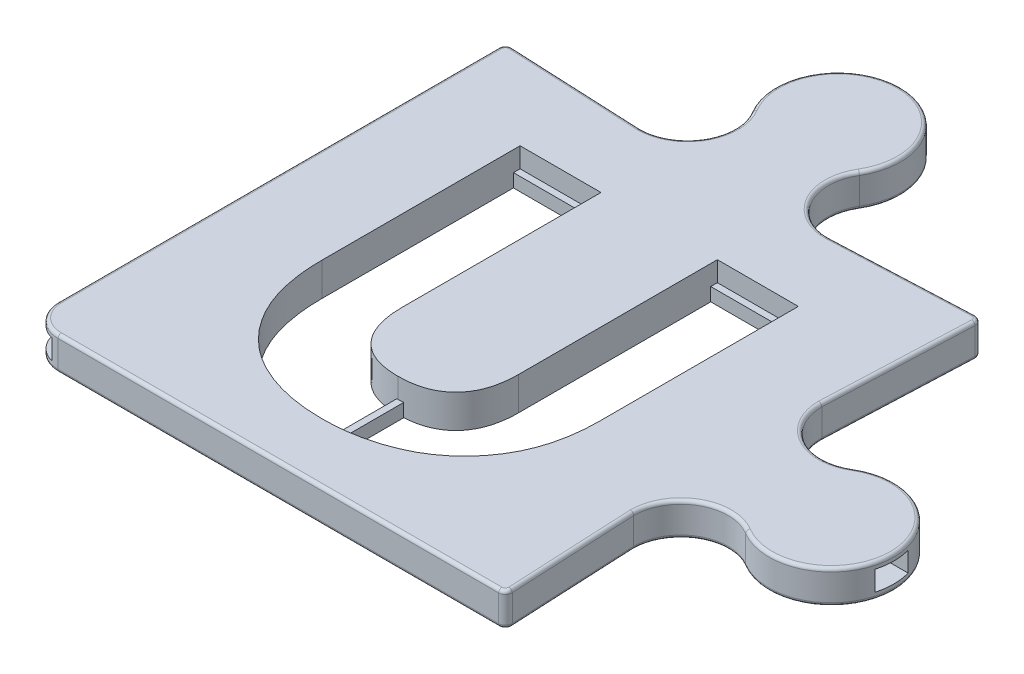
SolidWorks part; units mm, degrees
ref_plane "Front Plane" through (0, 0, 0) normal (0, 0, 1) x (1, 0, 0)
ref_plane "Top Plane" through (0, 0, 0) normal (0, 1, 0) x (1, 0, 0)
ref_plane "Right Plane" through (0, 0, 0) normal (1, 0, 0) x (0, 0, -1)
sketch "Sketch1" plane through (0, 0, 0) normal (0, 1, 0) x (1, 0, 0)
  line L0 (-31, -36) -> (37, -36) construction
  line L1 (-36, 37) -> (-36, -31) construction
  line L2 (-14.1421, 36) -> (-36, 37) construction
  line L3 (37, 37) -> (14.1421, 36) construction
  line L4 (36, 13.1421) -> (37, 37) construction
  line L5 (37, -36) -> (36, -15.1421) construction
  line L6 (-35.4, 36.3719) -> (-35.4, -31)
  line L7 (-36, 36) -> (36, 36) construction
  line L8 (-36, 36) -> (-36, -36) construction
  line L9 (-36, -36) -> (36, -36) construction
  line L10 (36, 36) -> (36, -36) construction
  line L11 (-31, -35.4) -> (36.3705, -35.4)
  line L12 (36.3705, -35.4) -> (35.4, -15.1568)
  line L13 (35.4, 13.155) -> (36.3732, 36.372)
  line L14 (36.3732, 36.372) -> (14.1555, 35.4)
  line L15 (-14.1562, 35.4) -> (-35.4, 36.3719)
  line L16 (-30, -24) -> (30, -24) construction
  line L17 (-30, 29) -> (30, 29) construction
  line L18 (-30, 29) -> (-30, -31) construction
  line L19 (-30, -31) -> (30, -31) construction
  line L20 (30, 29) -> (30, -31) construction
  line L21 (-30, 24) -> (30, 24) construction
  line L22 (-30, 24) -> (-30, -26) construction
  line L23 (-30, -26) -> (30, -26) construction
  line L24 (30, 24) -> (30, -26) construction
  arc A0 (-36, -31) -> (-31, -36) centre (-31, -31) ccw construction
  arc A1 (-14.1421, 36) -> (-8.571, 45.8485) centre (-14.1421, 42.5) ccw construction
  arc A2 (8.571, 45.8485) -> (-8.571, 45.8485) centre (0, 51) ccw construction
  arc A3 (8.571, 45.8485) -> (14.1421, 36) centre (14.1421, 42.5) ccw construction
  arc A4 (36, 13.1421) -> (45.8485, 7.571) centre (42.5, 13.1421) ccw construction
  arc A5 (45.8485, -9.571) -> (45.8485, 7.571) centre (51, -1) ccw construction
  arc A6 (45.8485, -9.571) -> (36, -15.1421) centre (42.5, -15.1421) ccw construction
  arc A7 (-35.4, -31) -> (-31, -35.4) centre (-31, -31) ccw
  arc A8 (46.1576, -9.0567) -> (35.4, -15.1568) centre (42.5, -15.1421) ccw
  arc A9 (46.1576, -9.0567) -> (46.1576, 7.0567) centre (51, -1) ccw
  arc A10 (35.4, 13.155) -> (46.1576, 7.0567) centre (42.5, 13.1421) ccw
  arc A11 (8.0567, 46.1576) -> (14.1555, 35.4) centre (14.1421, 42.5) ccw
  arc A12 (8.0567, 46.1576) -> (-8.0567, 46.1576) centre (0, 51) ccw
  arc A13 (-14.1562, 35.4) -> (-8.0567, 46.1576) centre (-14.1421, 42.5) ccw
  point P32 (36, 0)
  point P34 (0, 36)
  dimension "D5" = 6.5
  dimension "D6" = 10
  dimension "D7" = 6.5
  dimension "D13" = 5
  dimension "D9" = 10
  dimension "D11" = 6.5
  dimension "D12" = 6.5
  dimension "D1" = 72
  dimension "D2" = 1
  dimension "D3" = 1
  dimension "D4" = 15
  dimension "D8" = 1
  dimension "D10" = 35
  dimension "D14" = 15
  dimension "D15" = 36
  dimension "D16" = 1
  dimension "D18" = 60
  dimension "D19" = 60
  dimension "D20" = 5
  dimension "D21" = 6
  dimension "D22" = 5
  dimension "D23" = 50
  dimension "D24" = 2
  dimension "D17" = 0.6
extrude "Boss-Extrude1" add sketch "Sketch1" along normal blind 5
sketch "Sketch6" plane through (0, 0, 0) normal (0, -1, 0) x (1, 0, 0)
  line L0 (-35.4, -36.3719) -> (-35.4, 31) construction
  line L1 (-35.4, 17.9) -> (-27.4, 17.9)
  line L2 (-35.4, 17.9) -> (-35.4, -16.1)
  line L3 (-35.4, -16.1) -> (-27.4, -16.1)
  line L4 (-27.4, 17.9) -> (-27.4, -16.1)
  line L5 (-31, 35.4) -> (36.3705, 35.4) construction
  line L6 (-35.4, 14.65) -> (-30.4, 14.65)
  line L7 (-35.4, 14.65) -> (-35.4, -12.85)
  line L8 (-35.4, -12.85) -> (-30.4, -12.85)
  line L9 (-30.4, 14.65) -> (-30.4, -12.85)
  point P15 (-27.4, 0.9)
  point P16 (-30.4, 0.9)
  line M28 (-35.4, 31) -> (-35.4, -36.3719)
  dimension "D1" = 8
  dimension "D2" = 20.75
  dimension "D3" = 27.5
  dimension "D4" = 5
  dimension "D5" = 34
extrude "Cut-Extrude3" cut sketch "Sketch6" against normal blind 3 from offset 1 contours L6 L9 L8 L3 L4 L1 M28 | L9 L6 L2 L8 region at (-29.8665, 0, 0.9) region at (-32.9, 0, 0.9) offset against normal yes
extrude "Cut-Extrude4" cut sketch "Sketch6<3>" against normal up to next contours L9 L6 L2 L8 region at (-32.9, 0, 0.9)
sketch "Sketch6<3>" plane through (0, 0, 0) normal (0, -1, 0) x (1, 0, 0) same geometry as "Sketch6"
sketch "Sketch8" plane through (0, 0, 0) normal (0, -1, 0) x (1, 0, 0)
  line L1 (-2.5, -51.4) -> (2.5, -51.4)
  line L2 (-2.5, -51.4) -> (-2.5, -60.4)
  line L3 (-2.5, -60.4) -> (2.5, -60.4)
  line L4 (2.5, -51.4) -> (2.5, -60.4)
  line L5 (51.4, 3.5) -> (60.4, 3.5)
  line L6 (51.4, 3.5) -> (51.4, -1.5)
  line L7 (51.4, -1.5) -> (60.4, -1.5)
  line L8 (60.4, 3.5) -> (60.4, -1.5)
  arc A0 (-8.0567, -46.1576) -> (8.0567, -46.1576) centre (0, -51) ccw construction
  arc A1 (46.1576, -7.0567) -> (46.1576, 9.0567) centre (51, 1) ccw construction
  point P4 (0, -60.4)
  point P13 (60.4, 1)
  dimension "D1" = 5
  dimension "D2" = 9
  dimension "D3" = 5
  dimension "D4" = 9
extrude "Cut-Extrude5" cut sketch "Sketch8" against normal blind 3 from offset 1 offset against normal yes
sketch "Sketch9" plane through (0, 0, 0) normal (0, -1, 0) x (1, 0, 0)
  line L0 (-31, 35.4) -> (36.3705, 35.4) construction
  line L1 (-35.4, 14.65) -> (-35.4, 31) construction
  line L2 (-31.7636, 35.3332) -> (-35.4, 31) construction
  line L3 (-33.2571, 29.735) -> (-30.0429, 33.565) construction
  line L4 (-30.0429, 33.565) -> (-33.2571, 29.735) construction
  line L5 (-30.0429, 33.565) -> (-32.7119, 35.8048)
  line L6 (-33.2571, 29.735) -> (-35.926, 31.9747)
  line L7 (-32.7119, 35.8048) -> (-35.926, 31.9747)
  circle A0 centre (-31.65, 31.65) radius 2.5
  arc A1 (-31, 35.4) -> (-35.4, 31) centre (-31, 31) ccw construction
  arc M41 (-31, 35.4) -> (-35.4, 31) centre (-31, 31) ccw
  dimension "D1" = 5
  dimension "D3" = 3.75
  dimension "D4" = 5.6569
  dimension "D2" = 3.75
extrude "Cut-Extrude6" cut sketch "Sketch9" against normal blind 3 from offset 1 contours A0 L5 L6 M41 | A0 L5 region at (-33.6239, 0, 33.3064) region at (-31.65, 0, 31.65) offset against normal yes
sketch "Sketch11" plane through (-35.4, 0, 0) normal (-1, 0, 0) x (0, 0, 1)
  line L0 (-13.155, 0) -> (-36.372, 0) construction
  line L1 (-25.1, 3) -> (-19.1, 3)
  line L2 (-25.1, 3) -> (-25.1, 1.5)
  line L3 (-25.1, 1.5) -> (-19.1, 1.5)
  line L4 (-19.1, 3) -> (-19.1, 1.5)
  line L5 (-16.1, 4) -> (-16.1, 1) construction
  line L6 (35.4, 0) -> (15.1568, 0) construction
  line L7 (20.9, 3) -> (26.9, 3)
  line L8 (20.9, 3) -> (20.9, 1.5)
  line L9 (20.9, 1.5) -> (26.9, 1.5)
  line L10 (26.9, 3) -> (26.9, 1.5)
  line L12 (17.9, 4) -> (17.9, 1) construction
  dimension "D1" = 3
  dimension "D2" = 1.5
  dimension "D3" = 3
  dimension "D4" = 6
  dimension "D5" = 3
  dimension "D6" = 1.5
  dimension "D7" = 6
  dimension "D8" = 3
fillet "Fillet1" radius 0.5 17 edges at (-35.4, 0, 22.825) (-34.1113, 0, 34.1113) (2.6853, 0, 35.4) (35.8853, 0, 25.2784) (38.9978, 0, 8.966) (60.4, 0, 1) (38.9986, 0, -6.9655) (35.8866, 0, -24.7635) (25.2643, 0, -35.886) (7.9657, 0, -38.9984) (0, 0, -60.4) (-7.9658, 0, -38.9981) (-24.7781, 0, -35.886) (-35.4, 0, -24.611) (-32.9, 0, -12.85) (-30.4, 0, 0.9) (-32.9, 0, 14.65)
fillet "Fillet2" radius 0.5 13 edges at (-7.9658, 5, -38.9981) (0, 5, -60.4) (7.9657, 5, -38.9984) (25.2643, 5, -35.886) (35.8866, 5, -24.7635) (38.9986, 5, -6.9655) (60.4, 5, 1) (38.9978, 5, 8.966) (35.8853, 5, 25.2784) (2.6853, 5, 35.4) (-34.1113, 5, 34.1113) (-35.4, 5, -2.686) (-24.7781, 5, -35.886)
fillet "Fillet3" radius 1 9 edges at (36.2202, 0.1464, -36.2187) (36.2202, 4.8536, -36.2187) (36.3732, 2.5, -36.372) (-35.2536, 0.1464, -36.2186) (-35.2536, 4.8536, -36.2186) (36.2169, 0.1464, 35.2536) (36.2169, 4.8536, 35.2536) (36.3705, 2.5, 35.4) (-35.4, 2.5, -36.3719)
extrude "Cut-Extrude9" cut sketch "Sketch11" against normal blind 3
chamfer "Chamfer1" distance 1 angle 50 2 edges at (-35.4, 1.5, 23.9) (-35.4, 1.5, -22.1) first distance on face at (-35.4, 2.25, -22.1)
sketch "Sketch12" plane through (0, 5, 0) normal (0, 1, 0) x (1, 0, 0)
  text T0 "U" font "Poppins" height 50
extrude "Cut-Extrude10" cut sketch "Sketch12" against normal through all
sketch "Sketch13" plane through (0, 0, 0) normal (0, -1, 0) x (1, 0, 0)
  line L0 (-8.6768, -24) -> (-8.6768, 5.9155) construction
  line L1 (-20.8574, -24) -> (-8.6768, -24)
  line L2 (-20.8574, -24) -> (-20.8574, -23)
  line L3 (-20.8574, -23) -> (-8.6768, -23)
  line L4 (-8.6768, -24) -> (-8.6768, -23)
  line L5 (21.0223, -24) -> (21.0223, 5.8434) construction
  line L6 (8.8417, -24) -> (21.0223, -24)
  line L7 (8.8417, -24) -> (8.8417, -23)
  line L8 (8.8417, -23) -> (21.0223, -23)
  line L9 (21.0223, -24) -> (21.0223, -23)
  line L10 (8.8417, 5.9155) -> (8.8417, -24) construction
  line L11 (-0.1583, 14.3519) -> (0.8417, 14.3519)
  line L12 (-0.1583, 14.3519) -> (-0.1583, 27.5774)
  line L13 (-0.1583, 27.5774) -> (0.8417, 27.5774)
  line L14 (0.8417, 14.3519) -> (0.8417, 27.5774)
  point P17 (8.8417, -24)
  dimension "D1" = 1
  dimension "D2" = 1
  dimension "D3" = 1
  dimension "D4" = 8
  dimension "D5" = 13.2255
  dimension "D6" = 14.3519
extrude "Boss-Extrude2" add sketch "Sketch13" against normal blind 2
